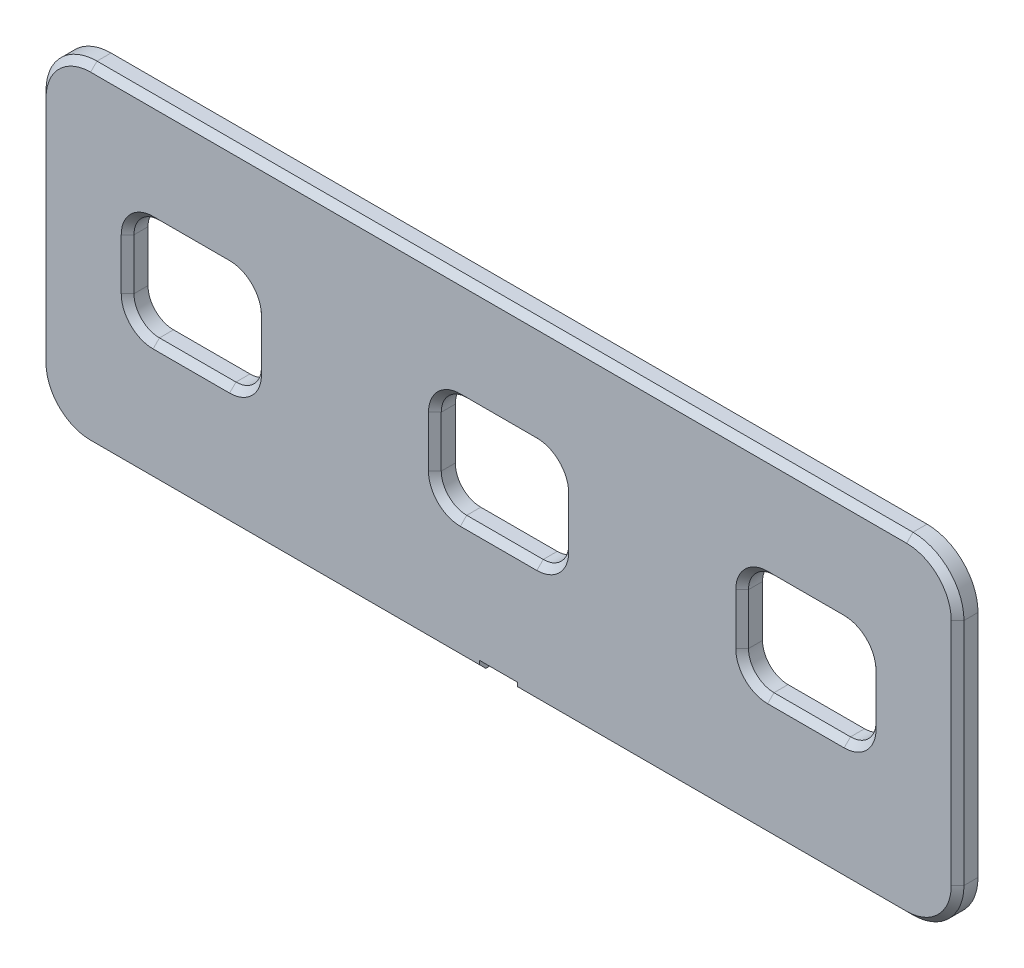
SolidWorks part; units mm, degrees
ref_plane "Front Plane" through (0, 0, 0) normal (0, 0, 1) x (1, 0, 0)
ref_plane "Top Plane" through (0, 0, 0) normal (0, 1, 0) x (1, 0, 0)
ref_plane "Right Plane" through (0, 0, 0) normal (1, 0, 0) x (0, 0, -1)
sketch "Sketch1" plane through (0, 0, 0) normal (0, 0, 1) x (1, 0, 0)
  line L0 (-32, 8.6) -> (32, 8.6)
  line L1 (36, 12.6) -> (36, 30.6)
  line L2 (32, 34.6) -> (-32, 34.6)
  line L3 (-36, 30.6) -> (-36, 12.6)
  arc A0 (-36, 12.6) -> (-32, 8.6) centre (-32, 12.6) ccw
  arc A1 (32, 8.6) -> (36, 12.6) centre (32, 12.6) ccw
  arc A2 (36, 30.6) -> (32, 34.6) centre (32, 30.6) ccw
  arc A3 (-32, 34.6) -> (-36, 30.6) centre (-32, 30.6) ccw
extrude "Boss-Extrude1" add sketch "Sketch1" along normal blind 1.6 from offset 78.4
chamfer "Chamfer1" distance 0.5 angle 45 8 edges at (0, 8.6, 80) (34.8284, 9.7716, 80) (-34.8284, 9.7716, 80) (36, 21.6, 80) (-36, 21.6, 80) (34.8284, 33.4284, 80) (-34.8284, 33.4284, 80) (0, 34.6, 80)
sketch "Sketch2" plane through (0, 0, 0) normal (0, 0, 1) x (1, 0, 0)
  line L0 (-3, 18.25) -> (3, 18.25)
  line L1 (5, 20.25) -> (5, 24.25)
  line L2 (3, 26.25) -> (-3, 26.25)
  line L3 (-5, 24.25) -> (-5, 20.25)
  arc A0 (-5, 20.25) -> (-3, 18.25) centre (-3, 20.25) ccw
  arc A1 (3, 18.25) -> (5, 20.25) centre (3, 20.25) ccw
  arc A2 (5, 24.25) -> (3, 26.25) centre (3, 24.25) ccw
  arc A3 (-3, 26.25) -> (-5, 24.25) centre (-3, 24.25) ccw
extrude "Boss-Extrude2" add sketch "Sketch2" along normal blind 3 from offset 78 separate body
combine bodies "Combine1" operation type subtract main body 101 bodies to subtract 102
chamfer "Chamfer2" distance 0.5 angle 45 8 edges at (0, 18.25, 80) (-4.4142, 18.8358, 80) (4.4142, 18.8358, 80) (-5, 22.25, 80) (5, 22.25, 80) (-4.4142, 25.6642, 80) (4.4142, 25.6642, 80) (0, 26.25, 80)
sketch "Sketch3" plane through (0, 0, 0) normal (0, 0, 1) x (1, 0, 0)
  line L0 (21.1, 18.25) -> (27.1, 18.25)
  line L1 (29.1, 20.25) -> (29.1, 24.25)
  line L2 (27.1, 26.25) -> (21.1, 26.25)
  line L3 (19.1, 24.25) -> (19.1, 20.25)
  arc A0 (19.1, 20.25) -> (21.1, 18.25) centre (21.1, 20.25) ccw
  arc A1 (27.1, 18.25) -> (29.1, 20.25) centre (27.1, 20.25) ccw
  arc A2 (29.1, 24.25) -> (27.1, 26.25) centre (27.1, 24.25) ccw
  arc A3 (21.1, 26.25) -> (19.1, 24.25) centre (21.1, 24.25) ccw
extrude "Boss-Extrude3" add sketch "Sketch3" along normal blind 3 from offset 78 separate body
combine bodies "Combine2" operation type subtract main body 103 bodies to subtract 104
chamfer "Chamfer3" distance 0.5 angle 45 8 edges at (24.1, 18.25, 80) (19.6858, 18.8358, 80) (28.5142, 18.8358, 80) (19.1, 22.25, 80) (29.1, 22.25, 80) (19.6858, 25.6642, 80) (28.5142, 25.6642, 80) (24.1, 26.25, 80)
sketch "Sketch4" plane through (0, 0, 0) normal (0, 0, 1) x (1, 0, 0)
  line L0 (-27.1, 18.25) -> (-21.1, 18.25)
  line L1 (-19.1, 20.25) -> (-19.1, 24.25)
  line L2 (-21.1, 26.25) -> (-27.1, 26.25)
  line L3 (-29.1, 24.25) -> (-29.1, 20.25)
  arc A0 (-29.1, 20.25) -> (-27.1, 18.25) centre (-27.1, 20.25) ccw
  arc A1 (-21.1, 18.25) -> (-19.1, 20.25) centre (-21.1, 20.25) ccw
  arc A2 (-19.1, 24.25) -> (-21.1, 26.25) centre (-21.1, 24.25) ccw
  arc A3 (-27.1, 26.25) -> (-29.1, 24.25) centre (-27.1, 24.25) ccw
extrude "Boss-Extrude4" add sketch "Sketch4" along normal blind 3 from offset 78 separate body
combine bodies "Combine3" operation type subtract main body 105 bodies to subtract 106
chamfer "Chamfer4" distance 0.5 angle 45 8 edges at (-24.1, 18.25, 80) (-28.5142, 18.8358, 80) (-19.6858, 18.8358, 80) (-29.1, 22.25, 80) (-19.1, 22.25, 80) (-28.5142, 25.6642, 80) (-19.6858, 25.6642, 80) (-24.1, 26.25, 80)
sketch "Sketch5" plane through (0, 0, 0) normal (0, 0, 1) x (1, 0, 0)
  line L1 (-1.5, 8.5) -> (1.5, 8.5)
  line L2 (-1.5, 8.5) -> (-1.5, 9.4)
  line L3 (-1.5, 9.4) -> (1.5, 9.4)
  line L4 (1.5, 8.5) -> (1.5, 9.4)
extrude "Boss-Extrude5" add sketch "Sketch5" along normal blind 0.9 from offset 79.2 separate body
combine bodies "Combine4" operation type subtract main body 107 bodies to subtract 108
sketch "Sketch6" plane through (0, 0, 0) normal (1, 0, 0) x (0, 0, -1)
  line L0 (-78.41, 12) -> (-74.6, 12)
  line L1 (-74.6, 12) -> (-74.6, 12.8)
  line L2 (-74.6, 12.8) -> (-74.9, 13.1)
  line L3 (-74.9, 13.1) -> (-75.2, 13.1)
  line L4 (-75.2, 13.1) -> (-75.2, 12.8)
  line L5 (-75.2, 12.8) -> (-78.41, 12.8)
  line L6 (-78.41, 12.8) -> (-78.41, 12)
extrude "Boss-Extrude6" add sketch "Sketch6" along normal blind 4 from offset 32 offset against normal yes
sketch "Sketch7" plane through (0, 0, 0) normal (1, 0, 0) x (0, 0, -1)
  line L0 (-78.41, 12) -> (-74.6, 12)
  line L1 (-74.6, 12) -> (-74.6, 12.8)
  line L2 (-74.6, 12.8) -> (-74.9, 13.1)
  line L3 (-74.9, 13.1) -> (-75.2, 13.1)
  line L4 (-75.2, 13.1) -> (-75.2, 12.8)
  line L5 (-75.2, 12.8) -> (-78.41, 12.8)
  line L6 (-78.41, 12.8) -> (-78.41, 12)
extrude "Boss-Extrude7" add sketch "Sketch7" along normal blind 4 from offset 28
